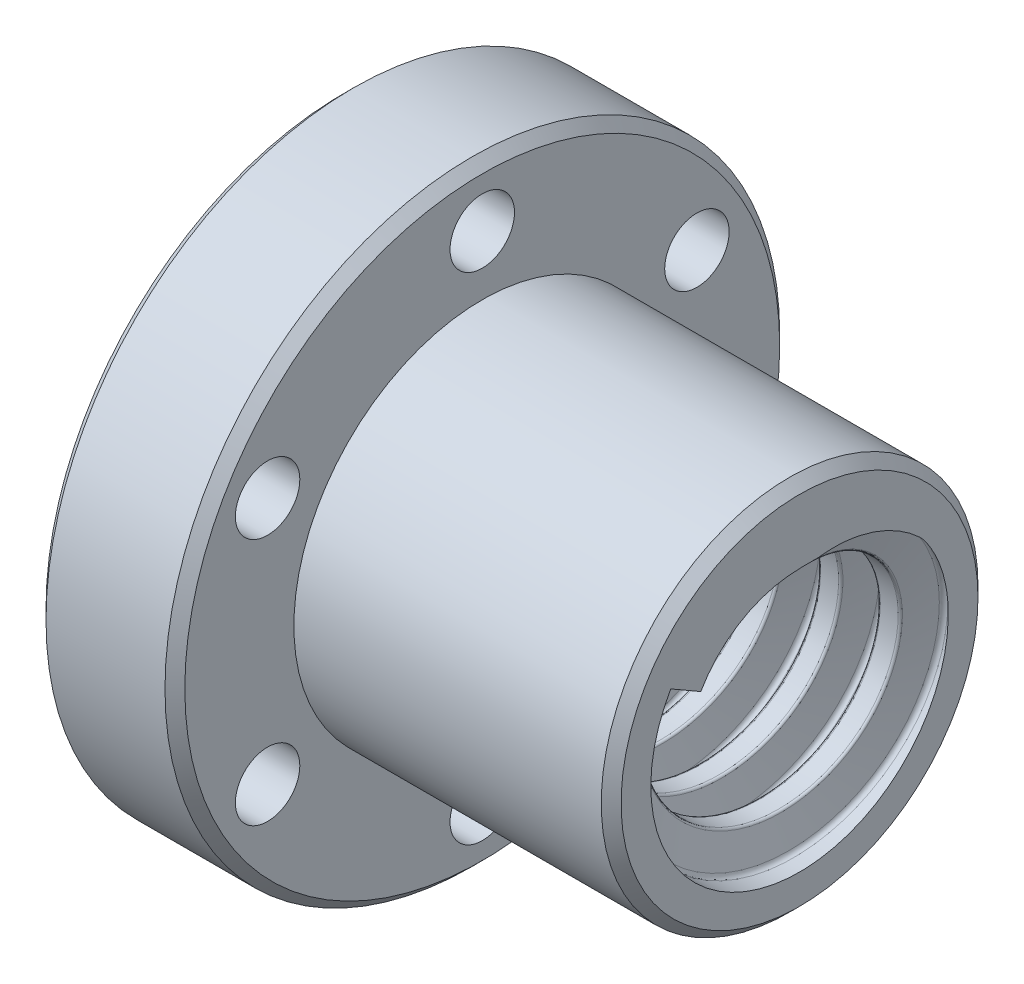
SolidWorks part; units mm, degrees
material "БрАЖ9-4 ГОСТ 18175-78"
ref_plane "Спереди" through (0, 0, 0) normal (0, 0, 1) x (1, 0, 0)
ref_plane "Сверху" through (0, 0, 0) normal (0, 1, 0) x (1, 0, 0)
ref_plane "Слева" through (0, 0, 0) normal (1, 0, 0) x (0, 0, -1)
sketch "Эскиз1" plane through (0, 0, 0) normal (0, 0, 1) x (1, 0, 0)
  line L0 (0, 0) -> (0, 31)
  line L1 (0, 31) -> (14, 31)
  line L2 (14, 31) -> (14, 19)
  line L3 (14, 19) -> (46, 19)
  line L4 (46, 19) -> (46, 0)
  line L5 (46, 0) -> (0, 0)
  line L6 (0, 0) -> (-24.9079, 0) construction
  dimension "D1" = 38
  dimension "D2" = 62
  dimension "D3" = 14
  dimension "D4" = 46
revolve "Повернуть1" add sketch "Эскиз1" angle 360 about L6
chamfer "Фаска1" distance 1 angle 45 3 edges at (46, 0, -19) (14, 0, -31) (0, 0, -31)
hole_wizard "Отверстие с зазором M61" positions "Эскиз3" profile "Эскиз2" hole size "M6" standard "ГОСТ" end condition up to next
sketch "Эскиз3" plane through (0, 0, 0) normal (-1, 0, 0) x (0, 0, 1)
  line L1 (0, 25) -> (-21.6506, 12.5) construction
  line L2 (-21.6506, 12.5) -> (-21.6506, -12.5) construction
  line L3 (-21.6506, -12.5) -> (0, -25) construction
  line L4 (0, -25) -> (21.6506, -12.5) construction
  line L5 (21.6506, -12.5) -> (21.6506, 12.5) construction
  line L6 (21.6506, 12.5) -> (0, 25) construction
  circle A0 centre (0, 0) radius 25 construction
  point P0 (21.6506, -12.5)
  point P15 (0, 25)
  point P17 (21.6506, 12.5)
  point P19 (0, -25)
  point P21 (-21.6506, -12.5)
  point P23 (-21.6506, 12.5)
  dimension "D1" = 50
sketch "Эскиз2" plane through (0, -12.5, 21.6506) normal (0, 1, 0) x (0, 0, 1)
  line L0 (0, 0) -> (0, 14)
  line L1 (0, 14) -> (3.25, 14)
  line L2 (3.25, 14) -> (3.25, 0)
  line L5 (3.25, 0) -> (0, 0)
  line L11 (0, -6.35) -> (0, 107.95) construction
  dimension "Диаметр сквозного отверстия" = 6.5
  dimension "Глубина сквозного отверстия" = 14
sketch "Эскиз4" plane through (0, 0, 0) normal (0, 0, 1) x (1, 0, 0)
  line L0 (0, -11.5) -> (0, -15) construction
  line L1 (-0.9062, -11.5) -> (0.9062, -11.5)
  line L2 (1.1477, -11.6853) -> (1.9366, -14.6294)
  line L3 (2.4196, -15) -> (-2.4196, -15)
  line L4 (-1.1477, -11.6853) -> (-1.9366, -14.6294)
  line L5 (-1.5, -13) -> (1.5, -13) construction
  line L6 (0, 0) -> (21.5695, 0) construction
  arc A0 (1.1477, -11.6853) -> (0.9062, -11.5) centre (0.9062, -11.75) ccw
  arc A1 (2.4196, -15) -> (1.9366, -14.6294) centre (2.4196, -14.5) cw
  arc A2 (-2.4196, -15) -> (-1.9366, -14.6294) centre (-2.4196, -14.5) ccw
  arc A3 (-1.1477, -11.6853) -> (-0.9062, -11.5) centre (-0.9062, -11.75) cw
  point P6 (0, -11.5)
  point P16 (0, -15)
  dimension "D1" = 0.25
  dimension "D2" = 0.5
  dimension "D3" = 3.5
  dimension "D4" = 1.5
  dimension "D5" = 3
  dimension "D6" = 30
  dimension "D7" = 30
sketch "Эскиз5" plane through (0, 0, 0) normal (-1, 0, 0) x (0, 0, 1)
  circle A0 centre (0, 0) radius 15
curve "Спираль1" pitch 6 height 46 turns 7.6667
sketch "Эскиз6" plane through (0, 0, 0) normal (-1, 0, 0) x (0, 0, 1)
  circle A0 centre (0, 0) radius 15
extrude "Вытянуть1" cut sketch "Эскиз6" against normal through all
sweep "По траектории1" add profiles "Эскиз4" path "Спираль1"
sketch "Эскиз7" plane through (0, 0, 0) normal (0, 0, 1) x (1, 0, 0)
  line L1 (0, 31) -> (46, 31)
  line L2 (0, 31) -> (0, -31)
  line L3 (0, -31) -> (46, -31)
  line L4 (46, 31) -> (46, -31)
  point P5 (46, 0)
extrude "Вытянуть2" cut sketch "Эскиз7" against normal through all and the other way through all flip side to cut
